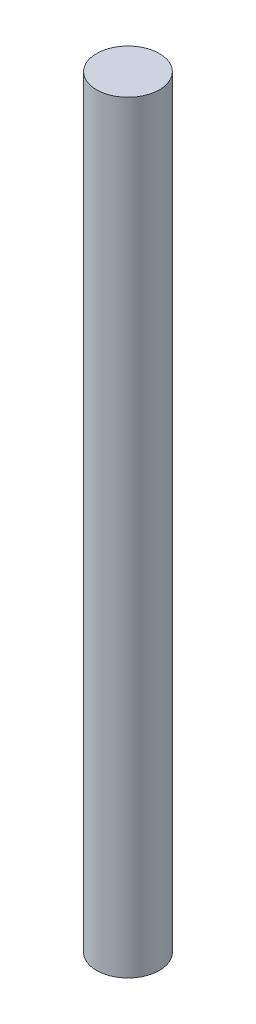
SolidWorks part; units mm, degrees
ref_plane "Front Plane" through (0, 0, 0) normal (0, 0, 1) x (1, 0, 0)
ref_plane "Top Plane" through (0, 0, 0) normal (0, 1, 0) x (1, 0, 0)
ref_plane "Right Plane" through (0, 0, 0) normal (1, 0, 0) x (0, 0, -1)
sketch "Elevation Bar" plane through (0, 0, 0) normal (0, 1, 0) x (1, 0, 0)
  circle A0 centre (0, 0) radius 30.226
  dimension "D1" = 60.452
extrude "Elevation Bar Part" add sketch "Elevation Bar" along normal blind 734.06
sketch "Pole and Drivetrain Pos" plane through (0, 0, 0) normal (0, 0, 1) x (1, 0, 0)
  line L0 (0, 0) -> (172.1794, 0) construction
  line L1 (-30.226, 0) -> (-30.226, 734.06) construction
  line L2 (-30.226, 734.06) -> (30.226, 734.06) construction
  line L3 (30.226, 734.06) -> (30.226, 0) construction
  line L4 (30.226, 0) -> (30.226, 734.06) construction
  line L5 (636.651, 40.7185) -> (27.051, 40.7185) construction
  line L6 (636.651, 53.4185) -> (27.051, 53.4185)
  line L7 (636.651, 53.4185) -> (636.651, 28.0185)
  line L8 (636.651, 28.0185) -> (27.051, 28.0185)
  line L9 (27.051, 53.4185) -> (27.051, 28.0185)
  line L10 (-30.226, 93.98) -> (30.226, 93.98) construction
  line L11 (33.2486, 0) -> (-33.2486, 0) construction
  line L12 (30.226, 185.42) -> (-30.226, 185.42) construction
  line L13 (30.226, 276.86) -> (-30.226, 276.86) construction
  line L14 (30.226, 368.3) -> (-30.226, 368.3) construction
  line L15 (30.226, 459.74) -> (-30.226, 459.74) construction
  line L16 (30.226, 551.18) -> (-30.226, 551.18) construction
  line L17 (30.226, 642.62) -> (-30.226, 642.62) construction
  line L18 (30.226, 73.152) -> (750.8896, 73.152) construction
  circle A0 centre (576.5632, 40.7185) radius 41.275 construction
  circle A1 centre (87.1388, 40.7185) radius 41.275 construction
  circle A2 centre (331.851, 40.7185) radius 41.275 construction
  point P24 (331.851, 40.7185)
  dimension "D2" = 82.55
  dimension "D1" = 609.6
  dimension "D3" = 25.4
  dimension "D4" = 244.7122
  dimension "D5" = 244.7122
  dimension "D6" = 93.98
  dimension "D7" = 185.42
  dimension "D8" = 276.86
  dimension "D9" = 368.3
  dimension "D10" = 459.74
  dimension "D11" = 551.18
  dimension "D12" = 642.62
  dimension "D13" = 73.152
sketch "Driving Wheels Geo" plane through (0, 0, 0) normal (0, 0, 1) x (1, 0, 0)
  line L0 (-30.226, 182.88) -> (-30.226, 101.727) construction
  line L1 (55.626, 101.727) -> (30.226, 101.727) construction
  line L2 (-30.226, 0) -> (-30.226, 734.06) construction
  line L3 (30.226, 734.06) -> (30.226, 0) construction
  line L5 (30.226, 101.727) -> (-30.226, 101.727) construction
  line L6 (-30.226, 182.88) -> (30.226, 101.727) construction
  line L7 (31.8135, 101.727) -> (-30.226, 182.88) construction
  line L8 (30.226, 226.8605) -> (203.668, 53.4185) construction
  line L9 (-55.626, 208.28) -> (31.6164, 208.28) construction
  line L10 (30.226, 73.152) -> (750.8896, 73.152) construction
  line L11 (636.651, 53.4185) -> (27.051, 53.4185) construction
  line L14 (-55.626, 157.48) -> (31.6164, 157.48) construction
  line L15 (31.6164, 157.48) -> (31.6164, 208.28) construction
  line L17 (18.9164, 208.28) -> (44.3164, 208.28) construction
  line L18 (18.9164, 208.28) -> (18.9164, 157.48) construction
  line L19 (18.9164, 157.48) -> (44.3164, 157.48) construction
  line L20 (44.3164, 208.28) -> (44.3164, 157.48) construction
  line L21 (18.9164, 208.28) -> (44.3164, 157.48) construction
  line L22 (18.9164, 157.48) -> (44.3164, 208.28) construction
  circle A1 centre (55.626, 101.727) radius 25.4
  circle A3 centre (-55.626, 182.88) radius 25.4
  circle A4 centre (81.026, 104.2185) radius 50.8 construction
  circle A5 centre (55.626, 101.727) radius 23.8125 construction
  point P16 (69.9877, 152.4)
  point P28 (31.6164, 182.88)
  point P30 (41.3076, 203.2)
  point P34 (38.2299, 203.2)
  dimension "D1" = 50.8
  dimension "D2" = 1.5875
  dimension "D3" = 52.603
  dimension "D4" = 3.175
  dimension "D5" = 182.88
  dimension "D8" = 101.6
  dimension "D6" = 50.8
  dimension "D13" = 3.175
  dimension "D7" = 81.153
  dimension "D9" = 45
  dimension "D10" = 53.317
  dimension "D11" = 25.4
  dimension "D12" = 48.3085
ref_plane "Plane1" through (0, 182.88, 0) normal (0, 1, 0) x (1, 0, 0)
sketch "Clamp Geo" plane through (0, 182.88, 0) normal (0, 1, 0) x (1, 0, 0)
  line L0 (-42.926, -19.8438) -> (-42.926, 50.8635) construction
  line L3 (27.051, 228.6) -> (27.051, -228.6) construction
  line L4 (50.0464, 31.8135) -> (-49.276, 31.8135)
  line L5 (50.0464, 31.8135) -> (50.0464, 50.8635)
  line L6 (50.0464, 50.8635) -> (-49.276, 50.8635)
  line L7 (-49.276, 31.8135) -> (-49.276, 50.8635)
  line L10 (-46.101, 50.8635) -> (-39.751, 50.8635)
  line L11 (-46.101, 50.8635) -> (-46.101, -19.8438)
  line L12 (-46.101, -19.8438) -> (-39.751, -19.8438)
  line L13 (-39.751, 50.8635) -> (-39.751, -19.8438)
  line L14 (-55.626, 12.7) -> (-30.226, 12.7) construction
  line L15 (-55.626, 12.7) -> (-55.626, -12.7) construction
  line L16 (-55.626, -12.7) -> (-30.226, -12.7) construction
  line L17 (-30.226, 12.7) -> (-30.226, -12.7) construction
  line L18 (-55.626, 12.7) -> (-30.226, -12.7) construction
  line L19 (-55.626, -12.7) -> (-30.226, 12.7) construction
  line L20 (0, -30.226) -> (0, 30.226) construction
  line L21 (-30.226, 0) -> (30.226, 0) construction
  line L22 (-46.101, 46.101) -> (-42.926, 46.101) construction
  line L23 (-39.751, 41.3385) -> (-46.101, 41.3385)
  line L24 (-46.101, 41.3385) -> (-46.101, 50.8635) construction
  line L25 (-39.751, 31.8135) -> (-39.751, 50.8635) construction
  line L26 (50.0464, 41.3385) -> (40.5214, 41.3385) construction
  circle A0 centre (0, 0) radius 30.226 construction
  circle A3 centre (-42.926, 46.101) radius 1.8288
  circle A5 centre (-42.926, 36.576) radius 1.8288
  circle A6 centre (40.5214, 41.3385) radius 6.35
  circle A7 centre (40.5214, 41.3385) radius 13.4704 construction
  point P14 (-42.926, 0)
  point P32 (-39.751, 41.3385)
  point P34 (-46.101, 41.3385)
  point P36 (-42.926, 41.3385)
  point P42 (50.0464, 41.3385)
  dimension "D1" = 60.452
  dimension "D4" = 1.5875
  dimension "D7" = 3.6576
  dimension "D8" = 3.175
  dimension "D10" = 12.7
  dimension "D11" = 3.175
  dimension "D2" = 457.2
  dimension "D3" = 19.05
  dimension "D5" = 6.35
  dimension "D6" = 25.4
  dimension "D9" = 99.3224
  dimension "D13" = 7.1437
sketch "Locked Setting Geo" plane through (0, 182.88, 0) normal (0, 1, 0) x (1, 0, 0)
  line L0 (30.2525, 144.301) -> (91.1428, 108.3583) construction
  line L1 (27.477, 37.9778) -> (77.9656, 123.5104)
  line L2 (27.477, 37.9778) -> (43.8821, 28.2941)
  line L3 (43.8821, 28.2941) -> (94.3707, 113.8267)
  line L4 (77.9656, 123.5104) -> (94.3707, 113.8267)
  line L5 (92.7568, 111.0925) -> (89.5289, 105.6242)
  line L6 (92.7568, 111.0925) -> (31.8664, 147.0352)
  line L7 (31.8664, 147.0352) -> (28.6385, 141.5668)
  line L8 (89.5289, 105.6242) -> (28.6385, 141.5668)
  line L9 (64.7337, 138.6948) -> (51.8221, 116.8213) construction
  line L10 (64.7337, 138.6948) -> (42.8602, 151.6064) construction
  line L11 (42.8602, 151.6064) -> (29.9486, 129.7329) construction
  line L12 (51.8221, 116.8213) -> (29.9486, 129.7329) construction
  line L13 (64.7337, 138.6948) -> (29.9486, 129.7329) construction
  line L14 (42.8602, 151.6064) -> (51.8221, 116.8213) construction
  line L17 (88.6555, 113.5135) -> (87.0416, 110.7793) construction
  line L18 (81.3263, 110.466) -> (84.5542, 115.9344)
  line L19 (84.5542, 115.9344) -> (92.7568, 111.0925) construction
  line L20 (73.1238, 115.3079) -> (89.5289, 105.6242) construction
  line L21 (35.6795, 33.1359) -> (40.5214, 41.3385) construction
  line L22 (50.0464, 50.8635) -> (-49.276, 50.8635) construction
  line L23 (-46.101, 50.8635) -> (-46.101, -19.8438) construction
  line L24 (27.051, 228.6) -> (27.051, -228.6) construction
  circle A1 centre (87.0416, 110.7793) radius 1.8288
  circle A2 centre (78.839, 115.6211) radius 1.8288
  circle A3 centre (40.5214, 41.3385) radius 6.35
  point P0 (28.8435, 138.8541)
  point P9 (0, 0)
  point P10 (47.3411, 134.2138)
  point P28 (81.3263, 110.466)
  point P30 (84.5542, 115.9344)
  point P32 (82.9403, 113.2002)
  point P36 (35.6795, 33.1359)
  point P39 (-49.276, 50.8635)
  point P40 (40.5214, 41.3385)
  point P41 (-39.7509, 50.7375)
  point P44 (-17.1792, 28.8062)
  point P45 (0, 0)
  point P49 (0, 0)
  point P50 (-42.9769, 45.6485)
  point P51 (0, 0)
  point P52 (0, 0)
  point P53 (-58.6924, 24.1175)
  point P54 (-34.6775, 57.1541)
  dimension "D6" = 3.6576
  dimension "D9" = 12.7
  dimension "D2" = 19.05
  dimension "D3" = 1.5875
  dimension "D4" = 6.35
  dimension "D5" = 25.4
  dimension "D7" = 3.175
  dimension "D8" = 99.3224
  dimension "D10" = 3.175
  dimension "D11" = 50.8635
  dimension "D12" = 67.3197
equation "\"D5@Pole and Drivetrain Pos\"=\"D4@Pole and Drivetrain Pos\""
